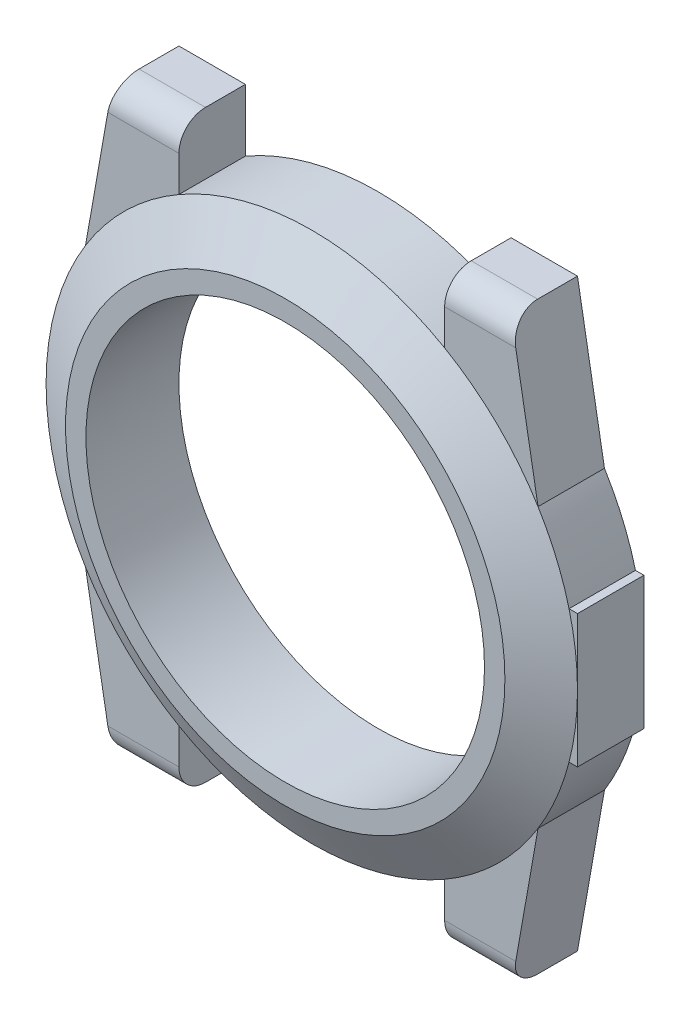
SolidWorks part; units mm, degrees
ref_plane "Plan de face" through (0, 0, 0) normal (0, 0, 1) x (1, 0, 0)
ref_plane "Plan de dessus" through (0, 0, 0) normal (0, 1, 0) x (1, 0, 0)
ref_plane "Plan de droite" through (0, 0, 0) normal (1, 0, 0) x (0, 0, -1)
sketch "Esquisse1" plane through (0, 0, 0) normal (0, 0, 1) x (1, 0, 0)
  line L0 (-10, 17.3205) -> (-10, 22)
  line L1 (-10, 22) -> (-15, 22)
  line L2 (-15, 22) -> (-17.0301, 10.487)
  line L3 (0, 0) -> (0, 27.8386) construction
  line L4 (10, 17.3205) -> (10, 22)
  line L5 (10, 22) -> (15, 22)
  line L6 (15, 22) -> (17.0301, 10.487)
  line L7 (0, 0) -> (34.0331, 0) construction
  line L8 (15, -22) -> (17.0301, -10.487)
  line L9 (10, -22) -> (15, -22)
  line L10 (10, -17.3205) -> (10, -22)
  line L11 (-10, -17.3205) -> (-10, -22)
  line L12 (-10, -22) -> (-15, -22)
  line L13 (-15, -22) -> (-17.0301, -10.487)
  line L14 (19.3649, 5) -> (20, 5)
  line L15 (20, 5) -> (20, -5)
  line L16 (20, -5) -> (19.3649, -5)
  arc A0 (-17.0301, 10.487) -> (-17.0301, -10.487) centre (0, 0) ccw
  circle A1 centre (0, 0) radius 15
  arc A2 (10, 17.3205) -> (-10, 17.3205) centre (0, 0) ccw
  arc A3 (17.0301, -10.487) -> (19.3649, -5) centre (0, 0) ccw
  arc A4 (-10, -17.3205) -> (10, -17.3205) centre (0, 0) ccw
  arc A5 (19.3649, 5) -> (17.0301, 10.487) centre (0, 0) ccw
  dimension "D1" = 40
  dimension "D6" = 30
  dimension "D2" = 5
  dimension "D3" = 80
  dimension "D4" = 20
  dimension "D5" = 44
  dimension "D7" = 10
extrude "Boss.-Extru.1" add sketch "Esquisse1" along normal blind 5
sketch "Esquisse5" plane through (0, 0, 5) normal (0, 0, 1) x (1, 0, 0)
  circle A0 centre (0, 0) radius 20
  circle A1 centre (0, 0) radius 15
  arc A6 (-17.0301, 10.487) -> (-17.0301, -10.487) centre (0, 0) ccw construction
  circle A7 centre (0, 0) radius 15 construction
extrude "Boss.-Extru.2" add sketch "Esquisse5" along normal blind 2
chamfer "Chanfrein2" distance 2 angle 60 1 edges at (20, 0, 7) first distance on face at (4.5191, -0.2381, 3.8095)
fillet "Congé1" radius 2 4 edges at (12.5, -22, 5) (-12.5, -22, 5) (12.5, 22, 5) (-12.5, 22, 5)
